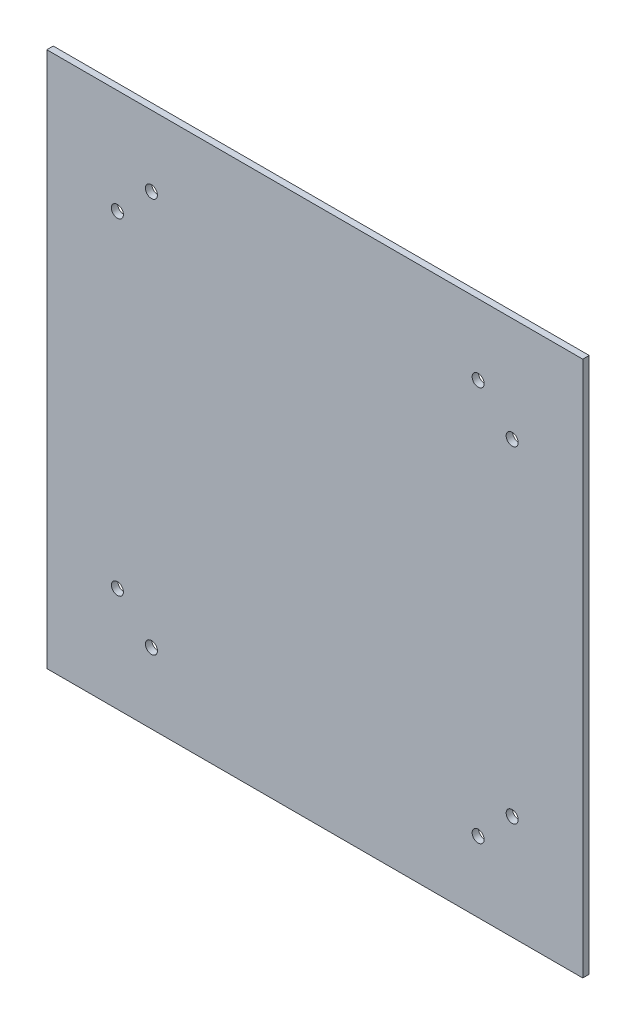
SolidWorks part; units mm, degrees
material "Custom Plastic"
ref_plane "Front Plane" through (0, 0, 0) normal (0, 0, 1) x (1, 0, 0)
ref_plane "Top Plane" through (0, 0, 0) normal (0, 1, 0) x (1, 0, 0)
ref_plane "Right Plane" through (0, 0, 0) normal (1, 0, 0) x (0, 0, -1)
sketch "Sketch1" plane through (0, 0, 0) normal (0, 0, 1) x (1, 0, 0)
  line L0 (0, -70.857) -> (0, 87.2635) construction
  line L1 (-94.5157, 0) -> (123.9998, 0) construction
  line L2 (62.5, 93.2079) -> (62.5, -95.5857) construction
  line L3 (-62.5, 98.439) -> (-62.5, -97.9634) construction
  line L4 (164.1839, -62.5) -> (-145.6374, -62.5) construction
  line L5 (158.0017, 62.5) -> (-146.593, 62.5) construction
  line L6 (-62.5, 62.5) -> (62.5, 62.5)
  line L7 (62.5, 62.5) -> (62.5, -62.5)
  line L8 (-62.5, 62.5) -> (-62.5, -62.5)
  line L9 (-62.5, -62.5) -> (62.5, -62.5)
  line L10 (46.0375, -92.075) -> (46.0375, 65.0875) construction
  line L11 (38.1, -103.1875) -> (38.1, 68.2625) construction
  line L12 (109.5375, -46.0375) -> (-92.0129, -46.0375) construction
  line L13 (111.125, -38.1) -> (-89.1956, -38.1) construction
  line L14 (-46.0375, -103.1875) -> (-46.0375, 68.2625) construction
  line L15 (-38.1, -98.425) -> (-38.1, 73.025) construction
  line L16 (101.6, 46.0375) -> (-93.6625, 46.0375) construction
  line L17 (101.6, 38.1) -> (-95.25, 38.1) construction
  circle A0 centre (46.0375, 38.1) radius 1.4
  circle A1 centre (38.1, 46.0375) radius 1.4
  circle A2 centre (-38.1, 46.0375) radius 1.4
  circle A3 centre (-46.0375, 38.1) radius 1.4
  circle A4 centre (-46.0375, -38.1) radius 1.4
  circle A5 centre (-38.1, -46.0375) radius 1.4
  circle A6 centre (38.1, -46.0375) radius 1.4
  circle A7 centre (46.0375, -38.1) radius 1.4
  dimension "D1" = 62.5
  dimension "D2" = 125
  dimension "D3" = 62.5
  dimension "D4" = 125
  dimension "D5" = 38.1
  dimension "D6" = 46.0375
  dimension "D7" = 46.0375
  dimension "D8" = 38.1
  dimension "D9" = 46.0375
  dimension "D10" = 38.1
  dimension "D11" = 38.1
  dimension "D12" = 46.0375
extrude "Extrude1" add sketch "Sketch1" along normal blind 1.5
